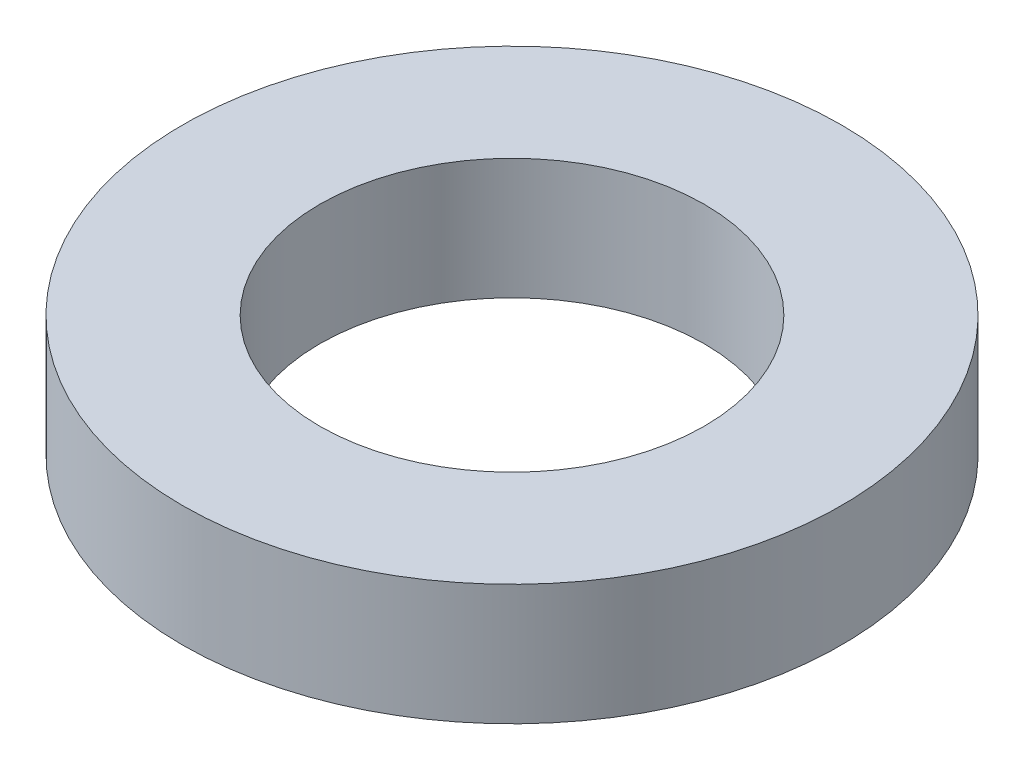
SolidWorks part; units mm, degrees
ref_plane "Front Plane" through (0, 0, 0) normal (0, 0, 1) x (1, 0, 0)
ref_plane "Top Plane" through (0, 0, 0) normal (0, 1, 0) x (1, 0, 0)
ref_plane "Right Plane" through (0, 0, 0) normal (1, 0, 0) x (0, 0, -1)
sketch "Sketch1" plane through (0, 0, 0) normal (0, 1, 0) x (1, 0, 0)
  circle A0 centre (0, 0) radius 60
  dimension "FLANGE_OD" = 120
extrude "Boss-Extrude1" add sketch "Sketch1" along normal blind 22
sketch "Sketch2" plane through (0, 0, 0) normal (0, 1, 0) x (1, 0, 0)
  circle A0 centre (0, 0) radius 35
  dimension "BORE_D" = 70
extrude "Cut-Extrude1" cut sketch "Sketch2" along normal through all
sketch "Sketch3" plane through (0, 22, 0) normal (0, 1, 0) x (1, 0, 0)
  circle A0 centre (0, 0) radius 21.4569 construction
  circle A1 centre (-21.4569, 0) radius 2.2834
  dimension "BOLT_D" = 4.5667
  dimension "BOLT_PCD" = 42.9139
extrude "Cut-Extrude2" cut sketch "Sketch3" against normal blind 20.4584 rebuild error yes
pattern_circular "CirPattern1" count 8 over 360 rebuild error yes
